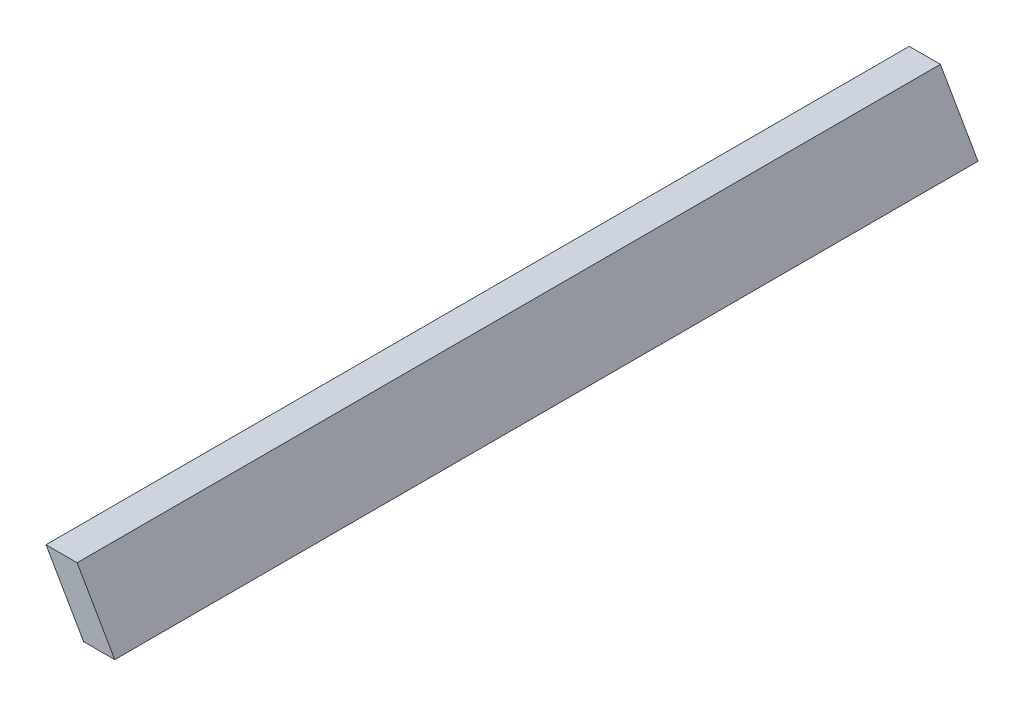
SolidWorks part; units mm, degrees
material "Gray Cast Iron"
ref_plane "Front Plane" through (0, 0, 0) normal (0, 0, 1) x (1, 0, 0)
ref_plane "Top Plane" through (0, 0, 0) normal (0, 1, 0) x (1, 0, 0)
ref_plane "Right Plane" through (0, 0, 0) normal (1, 0, 0) x (0, 0, -1)
sketch "Sketch6" plane through (0, 0, 0) normal (0, 0, 1) x (1, 0, 0)
  line B0 (-32.3728, -15.875) -> (94.6272, -15.875)
  line B1 (94.6272, 0) -> (69.5868, 0)
  line B2 (78.7522, 15.875) -> (47.1836, 15.875)
  line B3 (-9.1654, 15.875) -> (0, 0)
  line B4 (0, 0) -> (-32.3728, 0)
  line B5 (-7.3323, 0) -> (-16.4978, 15.875)
  line B6 (-16.4978, 15.875) -> (-9.1654, 15.875)
  line B7 (15.0709, 15.875) -> (15.0709, -3.175)
  line B8 (15.0709, -3.175) -> (47.1836, -3.175)
  line B9 (47.1836, -3.175) -> (47.1836, 15.875)
  line B10 (15.0709, 15.875) -> (-9.1654, 15.875)
  line B11 (-32.3728, 0) -> (-32.3728, 31.75)
  line B12 (-32.3728, 31.75) -> (94.6272, 31.75)
  line B13 (94.6272, 31.75) -> (94.6272, 0)
  line B14 (15.0709, 15.875) -> (47.1836, 15.875)
  line B15 (31.1272, 31.75) -> (31.1272, -15.875) construction
  line B16 (-7.3323, 0) -> (69.5868, 0) construction
  line B17 (2.4252, 21.082) -> (59.8292, 21.082) construction
  line B18 (5.7272, -8.001) -> (56.5272, -8.001) construction
  line B19 (5.7272, -8.001) -> (5.7272, 7.9375) construction
  line B20 (56.5272, -8.001) -> (56.5272, 7.9375) construction
  line B21 (-21.7048, 7.9375) -> (83.9592, 7.9375) construction
  circle B22 centre (31.1272, 6.35) radius 18.669 construction
sketch_block_instance "dovetail pair-1"
sketch_block "dovetail pair" parameters "D8"=37.338, "D1"=60, "D2"=127, "D3"=6.35, "D4"=15.875, "D5"=31.75, "D6"=95.25, "D7"=19.05, "D9"=60, "D10"=31.75, "D11"=50.8, "D12"=23.876, "D13"=7.874, "D14"=10.668, "D15"=34.798, "D16"=21.082, "D17"=7.9375
sketch "end-profile" plane through (0, 0, 0) normal (0, 0, 1) x (1, 0, 0)
  line L0 (0, 0) -> (-7.3323, 0) construction
  line L1 (-8.8721, 15.367) -> (-16.2045, 15.367)
  line L2 (-16.2045, 15.367) -> (-7.3505, 0.0314)
  line L3 (-7.3505, 0.0314) -> (-0.0181, 0.0314)
  line L4 (-9.1654, 15.875) -> (0, 0) construction
  line L5 (-16.4978, 15.875) -> (-9.1654, 15.875) construction
  line L6 (-7.3323, 0) -> (-16.4978, 15.875) construction
  line L7 (-9.1654, 15.875) -> (0, 0) construction
  line L8 (-16.4978, 15.875) -> (-9.1654, 15.875) construction
  line L9 (-7.3323, 0) -> (-16.4978, 15.875) construction
  line L10 (-0.0181, 0.0314) -> (-8.8721, 15.367)
  dimension "D1" = 0.508
extrude "Boss-Extrude1" add sketch "end-profile" along normal blind 203.2
ref_plane "screw pocket Plane1" through (-16.2045, 0, 0) normal (1, 0, 0) x (0, 0, -1)
sketch "Sketch4" plane through (-16.2045, 0, 0) normal (1, 0, 0) x (0, 0, -1)
  line L0 (0, 7.6992) -> (-203.2, 7.6992) construction
  line L3 (-181.1871, 7.6992) -> (-181.1871, 0.0314)
  line L4 (-181.1871, 0.0314) -> (-174.4129, 0.0314)
  line L5 (-174.4129, 0.0314) -> (-174.4129, 7.6992)
  line L6 (-143.0871, 7.6992) -> (-143.0871, 0.0314)
  line L7 (-143.0871, 0.0314) -> (-136.3129, 0.0314)
  line L8 (-136.3129, 0.0314) -> (-136.3129, 7.6992)
  line L9 (-104.9871, 7.6992) -> (-104.9871, 0.0314)
  line L10 (-104.9871, 0.0314) -> (-98.2129, 0.0314)
  line L11 (-98.2129, 0.0314) -> (-98.2129, 7.6992)
  line L12 (-66.8871, 7.6992) -> (-66.8871, 0.0314)
  line L13 (-66.8871, 0.0314) -> (-60.1129, 0.0314)
  line L14 (-60.1129, 0.0314) -> (-60.1129, 7.6992)
  line L15 (-28.7871, 7.6992) -> (-28.7871, 0.0314)
  line L16 (-28.7871, 0.0314) -> (-22.0129, 0.0314)
  line L17 (-22.0129, 0.0314) -> (-22.0129, 7.6992)
  line L18 (-181.1871, 7.6992) -> (-143.0871, 7.6992) construction
  line L20 (-203.2, 0.0314) -> (-203.2, 15.367) construction
  line L22 (0, 0.0314) -> (0, 15.367) construction
  line L23 (-203.2, 0.0314) -> (0, 0.0314) construction
  arc A0 (-174.4129, 7.6992) -> (-181.1871, 7.6992) centre (-177.8, 7.6992) ccw
  arc A1 (-136.3129, 7.6992) -> (-143.0871, 7.6992) centre (-139.7, 7.6992) ccw
  arc A2 (-98.2129, 7.6992) -> (-104.9871, 7.6992) centre (-101.6, 7.6992) ccw
  arc A3 (-60.1129, 7.6992) -> (-66.8871, 7.6992) centre (-63.5, 7.6992) ccw
  arc A4 (-22.0129, 7.6992) -> (-28.7871, 7.6992) centre (-25.4, 7.6992) ccw
  dimension "D1" = 6.7742
  dimension "D2" = 38.1
  dimension "D3" = 5
extrude "Cut-Extrude1" cut sketch "Sketch4" along normal blind 7.112
sketch "Sketch5" [suppressed] plane through (-16.2045, 0, 0) normal (1, 0, 0) x (0, 0, -1)
  line L0 (0, 7.6992) -> (-127, 7.6992) construction
  line L1 (-127, 0.0314) -> (-127, 15.367) construction
  line L2 (0, 0.0314) -> (0, 15.367) construction
  line L3 (-104.9871, 7.6992) -> (-104.9871, 0.0314)
  line L4 (-127, 0.0314) -> (0, 0.0314) construction
  line L5 (-104.9871, 0.0314) -> (-98.2129, 0.0314)
  line L6 (-98.2129, 0.0314) -> (-98.2129, 7.6992)
  line L7 (-66.8871, 7.6992) -> (-66.8871, 0.0314)
  line L8 (-66.8871, 0.0314) -> (-60.1129, 0.0314)
  line L9 (-60.1129, 0.0314) -> (-60.1129, 7.6992)
  line L10 (-28.7871, 7.6992) -> (-28.7871, 0.0314)
  line L11 (-28.7871, 0.0314) -> (-22.0129, 0.0314)
  line L12 (-22.0129, 0.0314) -> (-22.0129, 7.6992)
  line L13 (-104.9871, 7.6992) -> (-66.8871, 7.6992) construction
  arc A0 (-98.2129, 7.6992) -> (-104.9871, 7.6992) centre (-101.6, 7.6992) ccw
  arc A1 (-60.1129, 7.6992) -> (-66.8871, 7.6992) centre (-63.5, 7.6992) ccw
  arc A2 (-22.0129, 7.6992) -> (-28.7871, 7.6992) centre (-25.4, 7.6992) ccw
  dimension "D1" = 6.7742
  dimension "D2" = 38.1
extrude "Cut-Extrude2" [suppressed] cut sketch "Sketch5" along normal blind 7.112
equation "\"dovetail-angle\" = 60"
equation "\"dovetail-stock-width\" = 5"
equation "\"dovetail-stock-height\" = 1.25"
equation "\"dovetail-depth\" = 0.5 * \"dovetail-stock-height\""
equation "\"dovetail-throat-width\" = \"dovetail-stock-width\" - (2 * \"dovetail-depth\")"
equation "\"delta-x\" = 6"
equation "\"delta-y\" = 3"
equation "\"delta-z\"= 2.5"
equation "\"acme-nut-height\"= 0.5"
equation "\"acme-nut-width\"= 0.75"
equation "\"gib-thickness\" = 0.25"
equation "\"x-slide-length\" = \"dovetail-stock-width\" + \"delta-x\""
equation "\"y-slide-length\" = \"dovetail-stock-width\" + \"delta-y\""
equation "\"dog-point-diam\" = .149"
equation "\"dog-point-length\" = .067"
equation "\"dovetail-double-height\" = 2 * \"dovetail-depth\" + 0.5"
equation "\"acme-major-diam\" = .5"
equation "\"acme-pitch-diam\" = 0.45"
equation "\"acme-minor-diam\" = 0.4"
equation "\"acme-nut-od\" = 1.47"
equation "\"acme-nut-length\" = 1"
equation "\"acme-nut-trim-height\" = .75"
equation "\"screw-bearing-od\" = 0.5"
equation "\"screw-bearing-length\" = .375"
equation "\"screw-bearing-id\" = .3125"
equation "\"end-plate-thickness\" = \"screw-bearing-length\""
equation "\"screw-add-length\" = 2 * \"end-plate-thickness\" + 1 + 0.5"
equation "\"x-screw-length\" = \"x-slide-length\" + \"screw-add-length\""
equation "\"y-screw-length\" = \"y-slide-length\" + \"screw-add-length\""
equation "\"acme-nut-mount-hole-space-horz\" = 0.95"
equation "\"acme-nut-mount-hole-space-vert\" = 0.5 * \"acme-nut-length\""
equation "\"vise-hole-center-dist\" = 6.75"
equation "\"wiper_plate_clearance\" = .03"
equation "\"dial-width\" = 0.5"
equation "\"quarter-twenty-free-fit\" = .2667"
equation "\"D1@Sketch4\"=\"quarter-twenty-free-fit\""
equation "\"D1@Sketch5\"=\"quarter-twenty-free-fit\""
equation "\"D2@dovetail pair\"=\"dovetail-stock-width\""
equation "\"D1@dovetail pair\"=\"dovetail-angle\""
equation "\"D3@dovetail pair\"=\"gib-thickness\""
equation "\"D4@dovetail pair\"=\"dovetail-depth\""
equation "\"D5@dovetail pair\"=\"dovetail-stock-height\""
equation "\"D6@dovetail pair\"=\"dovetail-throat-width\""
equation "\"D10@dovetail pair\"=\"dovetail-stock-height\""
equation "\"D7@dovetail pair\"=\"acme-nut-trim-height\""
equation "\"D8@dovetail pair\"=\"acme-nut-od\""
equation "\"D9@dovetail pair\"=\"dovetail-angle\""
equation "\"D17@dovetail pair\"=\"dovetail-depth\"/2"
equation "\"acme-nut-trim-width\" = 1.25"
equation "\"acme_nut_clearance\" = .02"
equation "\"dovetail_male_clearance\" = .02"
equation "\"D1@end-profile\"=\"dovetail_male_clearance\""
